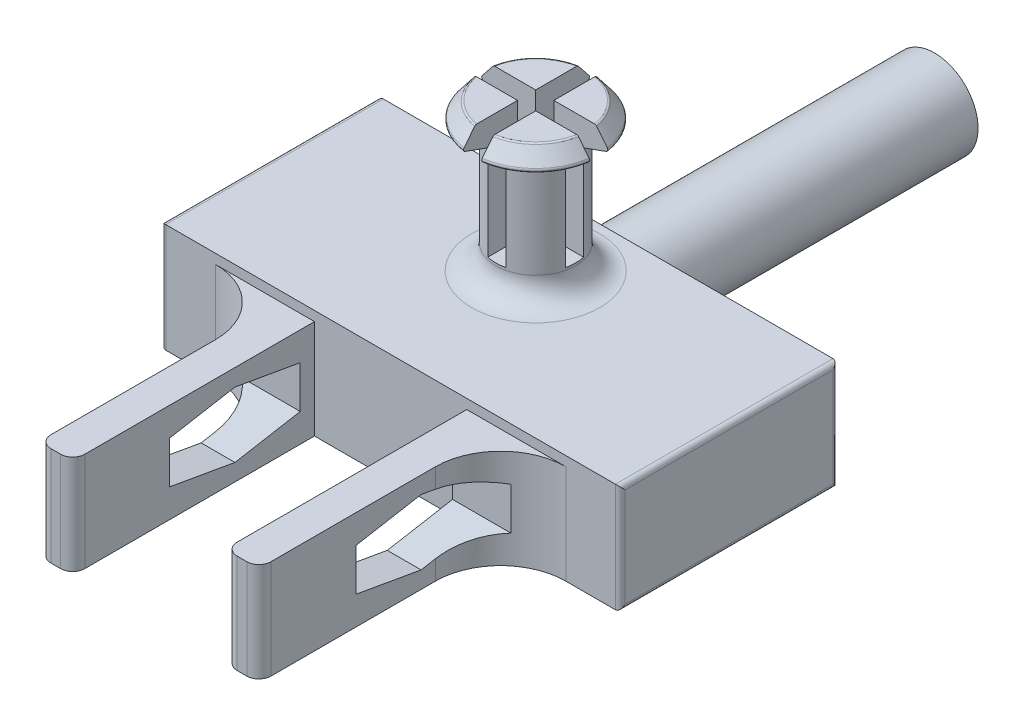
SolidWorks part; units mm, degrees
ref_plane "Front Plane" through (0, 0, 0) normal (0, 0, 1) x (1, 0, 0)
ref_plane "Top Plane" through (0, 0, 0) normal (0, 1, 0) x (1, 0, 0)
ref_plane "Right Plane" through (0, 0, 0) normal (1, 0, 0) x (0, 0, -1)
sketch "Szkic1" plane through (0, 0, 0) normal (0, 1, 0) x (1, 0, 0)
  line L0 (0, -13.1707) -> (0, 4.5) construction
  line L1 (4.55, -4.5) -> (-4.55, -4.5)
  line L2 (9.5, -4.5) -> (9.5, 4.5)
  line L3 (9.5, 4.5) -> (-9.5, 4.5)
  line L4 (-9.5, -4.5) -> (-9.5, 4.5)
  line L5 (9.5, -4.5) -> (-9.5, 4.5) construction
  line L6 (9.5, 4.5) -> (-9.5, -4.5) construction
  line L7 (-9.5, -4.5) -> (-4.55, -4.5)
  line L10 (2.5793, 4.5) -> (-2.5793, 4.5)
  line L13 (-4.55, -4.5) -> (-7.25, -4.5)
  line L14 (-4.55, -4.5) -> (-3.15, -4.5)
  line L15 (-4.55, -4.5) -> (-4.55, -14.5)
  line L16 (-4.55, -14.5) -> (-3.15, -14.5)
  line L17 (-3.15, -4.5) -> (-3.15, -14.5)
  line L18 (4.55, -4.5) -> (3.15, -4.5)
  line L19 (4.55, -4.5) -> (4.55, -14.5)
  line L20 (4.55, -14.5) -> (3.15, -14.5)
  line L21 (3.15, -4.5) -> (3.15, -14.5)
  line L22 (4.55, -4.5) -> (9.5, -4.5)
  line L23 (-4.55, -4.5) -> (-4.55, -7.2)
  line L26 (4.55, -4.5) -> (7.25, -4.5)
  line L27 (4.55, -4.5) -> (4.55, -7.2)
  arc A0 (-4.55, -7.2) -> (-7.25, -4.5) centre (-7.25, -7.2) ccw
  arc A1 (7.25, -4.5) -> (4.55, -7.2) centre (7.25, -7.2) ccw
  point P0 (0, 0)
  dimension "D1" = 9
  dimension "D2" = 19
  dimension "D3" = 10
  dimension "D4" = 1.4
  dimension "D5" = 6.3
  dimension "D6" = 2.7
extrude "Dodanie-wyciągnięcie1" add sketch "Szkic1" along normal blind 4.5 contours L1 L22 L2 L3 L4 L7 region at (0, 0, 0)
extrude "Dodanie-wyciągnięcie2" add sketch "Szkic1<7>" along normal blind 4.1 contours A0 L15 L7 | L17 L1 L15 L16 | A1 L22 L19 | L1 L21 L20 L19 region at (3.85, 0, 9.5) region at (5.1531, 0, 5.1031) region at (-3.85, 0, 9.5) region at (-5.1531, 0, 5.1031)
sketch "Szkic1<7>" plane through (0, 0, 0) normal (0, 1, 0) x (1, 0, 0) same geometry as "Szkic1"
ref_plane "Płaszczyzna1" through (0, 0, -4.5) normal (0, 0, -1) x (-1, 0, 0)
sketch "Szkic2" plane through (0, 0, -4.5) normal (0, 0, -1) x (-1, 0, 0)
  line L0 (0, 0) -> (0, 4.5) construction
  line L1 (-9.5, 4.5) -> (9.5, 4.5) construction
  circle A0 centre (0, 2.25) radius 1.8
  point P5 (0, 2.25)
  dimension "D1" = 3.6
extrude "Dodanie-wyciągnięcie3" add sketch "Szkic2" along normal blind 13.5
ref_plane "Płaszczyzna2" through (-3.15, 0, 0) normal (1, 0, 0) x (0, 0, -1)
sketch "Szkic3" plane through (-3.15, 0, 0) normal (1, 0, 0) x (0, 0, -1)
  line L0 (-7.79, 3.4) -> (-10.49, 2.9239)
  line L1 (-10.49, 2.9239) -> (-10.49, 1.1761)
  line L2 (-10.49, 1.1761) -> (-7.79, 0.7)
  line L3 (-7.79, 0.7) -> (-5.09, 1.1761)
  line L4 (-5.09, 1.1761) -> (-5.09, 2.9239)
  line L5 (-5.09, 2.9239) -> (-7.79, 3.4)
  line L7 (-4.5, 4.1) -> (-14.5, 4.1) construction
  line L8 (-4.5, 0) -> (-14.5, 0) construction
  dimension "D1" = 0.7
  dimension "D2" = 0.7
  dimension "D3" = 100
  dimension "D4" = 100
  dimension "D5" = 5.4
extrude "Wytnij-wyciągnięcie2" cut sketch "Szkic3" along normal through all both and the other way through all
fillet "Zaokrąglenie1" radius 0.5 4 edges at (3.15, 2.05, 14.5) (4.55, 2.05, 14.5) (-4.55, 2.05, 14.5) (-3.15, 2.05, 14.5)
fillet "Zaokrąglenie2" radius 0.2 8 edges at (-9.5, 2.25, -4.5) (-9.5, 4.5, 0) (9.5, 0, 0) (-9.5, 2.25, 4.5) (9.5, 2.25, 4.5) (9.5, 2.25, -4.5) (9.5, 4.5, 0) (-9.5, 0, 0)
ref_plane "Płaszczyzna3" through (0, 4.5, 0) normal (0, 1, 0) x (1, 0, 0)
sketch "Szkic4" plane through (0, 4.5, 0) normal (0, 1, 0) x (1, 0, 0)
  line L0 (-9.3, 1.5) -> (9.3, 1.5) construction
  line L1 (2.475, 4.5) -> (-2.475, 4.5) construction
  line L3 (-9.3, 4.5) -> (-9.3, -4.5) construction
  line L4 (9.3, -4.5) -> (9.3, 4.5) construction
  circle A0 centre (0, 1.5) radius 1.65
  point P6 (0, 1.5)
  dimension "D1" = 3.3
  dimension "D2" = 3
extrude "Dodanie-wyciągnięcie4" add sketch "Szkic4" along normal blind 5.1
ref_plane "Płaszczyzna4" through (0, 9.6, 0) normal (0, 1, 0) x (1, 0, 0)
sketch "Szkic5" plane through (0, 9.6, 0) normal (0, 1, 0) x (1, 0, 0)
  line L0 (0, 3.15) -> (0, -0.15) construction
  circle A0 centre (0, 1.5) radius 1.65 construction
  circle A1 centre (0, 1.5) radius 1.65
  point P5 (0, 1.5)
  dimension "D1" = 3.3
extrude "Dodanie-wyciągnięcie5" add sketch "Szkic5" along normal blind 1
fillet "Zaokrąglenie4" radius 1 1 edges at (0, 4.5, 0.15)
ref_axis "Oś1" through (0, 16.6, -1.5) along (0, -1, 0)
ref_point "Punkt1"
ref_point "Punkt2"
ref_plane "Płaszczyzna5" through (0, 0, 0) normal (1, 0, 0) x (0, 0, -1)
ref_plane "Płaszczyzna Dolnia" through (0, 0, 0) normal (0, -1, 0) x (-1, 0, 0)
ref_plane "Płaszczyzna6" through (0, 10.5, 0) normal (0, 1, 0) x (1, 0, 0)
ref_plane "Płaszczyzna7" through (0, 10.6, 0) normal (0, 1, 0) x (1, 0, 0)
sketch "Szkic6" plane through (0, 10.6, 0) normal (0, 1, 0) x (1, 0, 0)
  line L0 (0.375, 4.6645) -> (0.375, 1.875)
  line L1 (-0.375, 4.6645) -> (-0.375, 1.875)
  line L2 (3.1645, 1.875) -> (0.375, 1.875)
  line L3 (3.1645, 1.125) -> (0.375, 1.125)
  line L4 (-0.375, 1.125) -> (-3.1645, 1.125)
  line L5 (-0.375, 1.875) -> (-3.1645, 1.875)
  line L6 (0.375, 1.125) -> (0.375, -1.6645)
  line L7 (-0.375, 1.125) -> (-0.375, -1.6645)
  line L8 (-0.375, 1.875) -> (0.375, 1.125) construction
  arc A4 (0.375, 4.6645) -> (-0.375, 4.6645) centre (0, 1.5) ccw
  arc A5 (3.1645, 1.125) -> (3.1645, 1.875) centre (0, 1.5) ccw
  arc A6 (-0.375, -1.6645) -> (0.375, -1.6645) centre (0, 1.5) ccw
  arc A7 (-3.1645, 1.875) -> (-3.1645, 1.125) centre (0, 1.5) ccw
  point P18 (0, 1.5)
  dimension "D1" = 0.75
  dimension "D2" = 0.75
sketch "Szkic7" plane through (0, 0, 0) normal (1, 0, 0) x (0, 0, -1)
  line L0 (3.15, 10.6) -> (3.65, 10.6)
  line L1 (4.6866, 10.6) -> (4.6645, 10.6) construction
  line L2 (3.15, 5.5) -> (3.15, 10.6) construction
  line L3 (3.65, 10.6) -> (4.1978, 9.9)
  line L4 (4.1978, 9.9) -> (3.15, 9.5186)
  line L6 (3.15, 5.5) -> (3.15, 10.6) construction
  line L7 (3.15, 9.5186) -> (3.15, 10.6)
  line L9 (3.15, 5.5) -> (3.15, 10.6) construction
  line L10 (3.15, 5.5) -> (3.15, 10.6) construction
  line L11 (3.15, 5.5) -> (3.15, 10.6) construction
  line L13 (4.95, 4.5) -> (-4.95, 4.5) construction
  dimension "D1" = 5.4
  dimension "D2" = 70
  dimension "D3" = 0.5
revolve "Obrót1" add sketch "Szkic7" angle 360 about axis through (0, 16.6, -1.5) along (0, -1, 0)
fillet "Zaokrąglenie5" radius 0.1 2 edges at (0, 10.6, 0.65) (0, 9.9, 1.1978)
extrude "Wytnij-wyciągnięcie3" cut sketch "Szkic6" against normal blind 5
